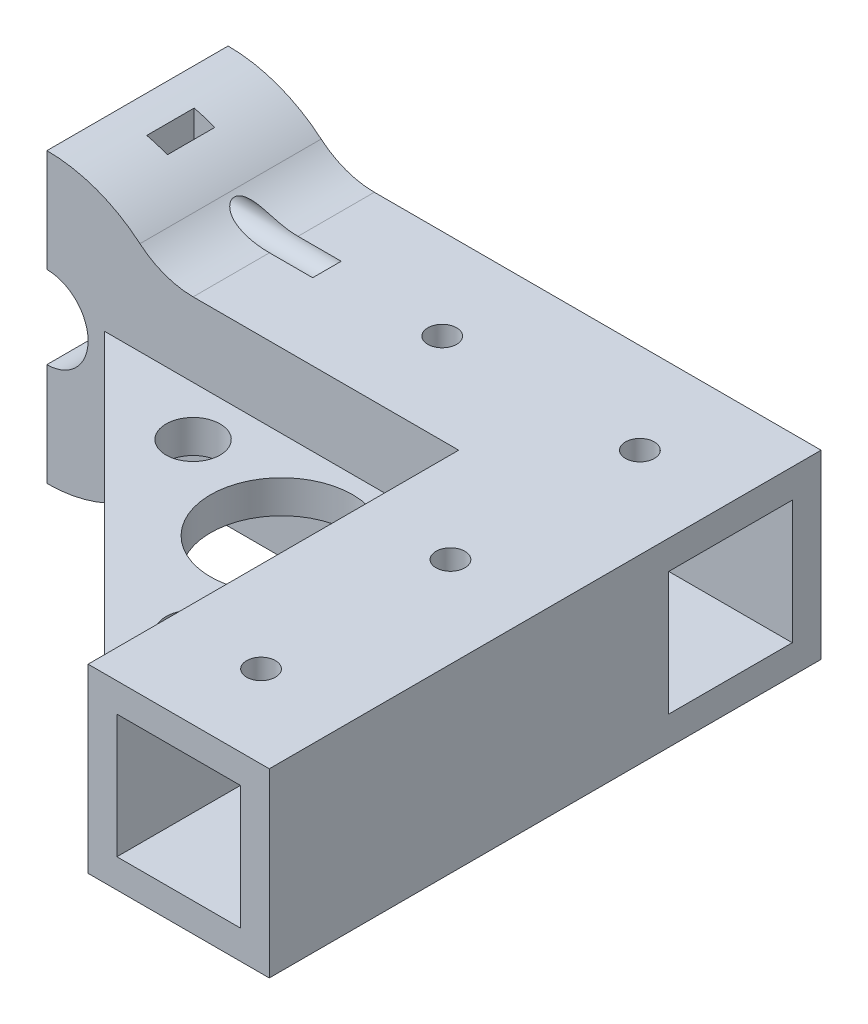
SolidWorks part; units mm, degrees
ref_plane "Front Plane" through (0, 0, 0) normal (0, 0, 1) x (1, 0, 0)
ref_plane "Top Plane" through (0, 0, 0) normal (0, 1, 0) x (1, 0, 0)
ref_plane "Right Plane" through (0, 0, 0) normal (1, 0, 0) x (0, 0, -1)
sketch "Sketch1" plane through (0, 0, 0) normal (0, 0, 1) x (1, 0, 0)
  line L0 (41.5599, 4.1233) -> (41.5599, -17.8767) construction
  line L1 (5.1706, 4.1233) -> (63.5599, 4.1233)
  line L2 (-8.4401, 7.6443) -> (-8.4401, -1.8767)
  line L3 (5.1706, -17.8767) -> (63.5599, -17.8767)
  line L4 (63.5599, 4.1233) -> (63.5599, -17.8767)
  line L5 (-8.4401, -11.8767) -> (-8.4401, -14.3557)
  line L6 (-8.4401, -14.3557) -> (-8.4401, -24.3767)
  line L7 (-8.4401, 7.6443) -> (-8.4401, 10.6233)
  arc A0 (-8.4401, -11.8767) -> (-8.4401, -1.8767) centre (-8.4401, -6.8767) ccw
  arc A1 (5.1706, 4.1233) -> (-8.4401, 10.6233) centre (-8.4401, -6.8767) ccw
  arc A2 (-8.4401, -24.3767) -> (5.1706, -17.8767) centre (-8.4401, -6.8767) ccw
  dimension "D4" = 10
  dimension "D5" = 35
  dimension "D1" = 22
  dimension "D2" = 50
  dimension "D3" = 22
  dimension "D6" = 11
extrude "Boss-Extrude1" add sketch "Sketch1" along normal blind 22
sketch "Sketch2" plane through (0, 0, 22) normal (0, 0, 1) x (1, 0, 0)
  line L0 (5.1706, -17.8767) -> (63.5599, -17.8767) construction
  line L1 (63.5599, 4.1233) -> (41.5599, 4.1233)
  line L2 (63.5599, 4.1233) -> (63.5599, -17.8767)
  line L3 (63.5599, -17.8767) -> (41.5599, -17.8767)
  line L4 (41.5599, 4.1233) -> (41.5599, -17.8767)
  dimension "D1" = 22
extrude "Boss-Extrude2" add sketch "Sketch2" along normal blind 45
sketch "Sketch3" plane through (0, 0, 67) normal (0, 0, 1) x (1, 0, 0)
  line L0 (63.5599, -17.8767) -> (63.5599, 4.1233) construction
  line L1 (45.0599, 0.6233) -> (60.0599, 0.6233)
  line L2 (45.0599, 0.6233) -> (45.0599, -14.3767)
  line L3 (45.0599, -14.3767) -> (60.0599, -14.3767)
  line L4 (60.0599, 0.6233) -> (60.0599, -14.3767)
  line L5 (63.5599, 4.1233) -> (41.5599, 4.1233) construction
  dimension "D1" = 15
  dimension "D2" = 3.5
  dimension "D3" = 15
  dimension "D4" = 3.5
extrude "Cut-Extrude1" cut sketch "Sketch3" against normal offset from surface (43 mm away) 2 up to face at (8.2716, -5.5017, 22)
sketch "Sketch4" plane through (63.5599, 0, 0) normal (1, 0, 0) x (0, 0, -1)
  line L0 (-67, 4.1233) -> (0, 4.1233) construction
  line L1 (-3.5, 0.6233) -> (-18.5, 0.6233)
  line L2 (-3.5, 0.6233) -> (-3.5, -14.3767)
  line L3 (-3.5, -14.3767) -> (-18.5, -14.3767)
  line L4 (-18.5, 0.6233) -> (-18.5, -14.3767)
  line L5 (0, -17.8767) -> (0, 4.1233) construction
  dimension "D1" = 15
  dimension "D2" = 15
  dimension "D3" = 3.5
  dimension "D4" = 3.5
extrude "Cut-Extrude2" cut sketch "Sketch4" against normal blind 45
ref_plane "Plane1" through (0, -6.8767, 0) normal (0, 1, 0) x (1, 0, 0)
sketch "Sketch6" plane through (0, -6.8767, 0) normal (0, 1, 0) x (1, 0, 0)
  line L0 (-1.4401, -22) -> (41.5599, -65)
  line L1 (41.5599, -22) -> (5.1706, -22) construction
  line L2 (41.5599, -67) -> (41.5599, -22) construction
  line L3 (41.5599, -65) -> (41.5599, -22)
  line L4 (41.5599, -22) -> (-1.4401, -22)
  line L5 (-3.4401, -22) -> (-3.4401, 0) construction
  dimension "D1" = 2
  dimension "D2" = 45
extrude "Boss-Extrude3" add sketch "Sketch6" along normal blind 2 and the other way blind 2
fillet "Fillet1" radius 10 2 edges at (5.1706, -17.8767, 11) (5.1706, 4.1233, 11)
sketch "Sketch5" plane through (-8.4401, 0, 0) normal (-1, 0, 0) x (0, 0, 1)
  line L0 (0, 4.3733) -> (22, 4.3733) construction
  line L1 (0, 10.6233) -> (0, -1.8767) construction
  line L2 (22, 10.6233) -> (22, -1.8767) construction
  line L3 (0, -18.1267) -> (22, -18.1267) construction
  line L4 (0, -11.8767) -> (0, -24.3767) construction
  line L5 (22, -11.8767) -> (22, -24.3767) construction
  circle A1 centre (11, 4.3733) radius 1.75
  circle A3 centre (11, -18.1267) radius 1.75
  dimension "D1" = 3.5
  dimension "D4" = 11
  dimension "D5" = 11
extrude "Cut-Extrude3" cut sketch "Sketch5" against normal blind 23
sketch "Sketch7" plane through (0, 4.1233, 0) normal (0, 1, 0) x (1, 0, 0)
  line L1 (14.5599, -9.2679) -> (14.5599, -12.7321) construction
  line L2 (-4.4401, -8.125) -> (-1.9401, -8.125)
  line L3 (-4.4401, -8.125) -> (-4.4401, -13.875)
  line L4 (-4.4401, -13.875) -> (-1.9401, -13.875)
  line L5 (-1.9401, -8.125) -> (-1.9401, -13.875)
  line L7 (-8.4401, -22) -> (-8.4401, 0) construction
  point P0 (14.5599, -11)
  dimension "D1" = 5.75
  dimension "D2" = 2.875
  dimension "D3" = 4
  dimension "D4" = 2.5
extrude "Cut-Extrude4" cut sketch "Sketch7" against normal blind 3.5 and the other way blind 10
mirror "Mirror1" about plane through (0, -6.8767, 0) normal (0, 1, 0) of "Cut-Extrude4"
sketch "Sketch8" plane through (0, -17.8767, 0) normal (0, -1, 0) x (1, 0, 0)
  line L0 (18.5599, 11) -> (63.5599, 11) construction
  line L1 (18.5599, 18.5) -> (18.5599, 3.5) construction
  line L2 (63.5599, 67) -> (63.5599, 0) construction
  line L3 (52.5599, 24) -> (52.5599, 67) construction
  line L4 (60.0599, 24) -> (45.0599, 24) construction
  line L5 (41.5599, 67) -> (63.5599, 67) construction
  circle A0 centre (28.5599, 11) radius 1.75
  circle A1 centre (52.5599, 11) radius 1.75
  circle A2 centre (52.5599, 34) radius 1.75
  circle A3 centre (52.5599, 57) radius 1.75
  dimension "D1" = 3.5
  dimension "D2" = 10
  dimension "D3" = 10
  dimension "D4" = 10
extrude "Cut-Extrude5" cut sketch "Sketch8" against normal up to surface (22 mm away) up to face at (29.2743, 4.1233, 24.45)
sketch "Sketch9" plane through (0, 0, 0) normal (0, 0, -1) x (-1, 0, 0)
  line L0 (-63.5599, -12.8767) -> (-9.3152, -12.8767) construction
  line L1 (-63.5599, -17.8767) -> (-63.5599, 4.1233) construction
  line L2 (-9.3152, -17.8767) -> (-63.5599, -17.8767) construction
  text T0 "  MR.3" font "Arial Narrow" height 12
  dimension "D1" = 5
extrude "Cut-Extrude6" cut sketch "Sketch9" against normal blind 1.5
sketch "Sketch10" plane through (0, -8.8767, 0) normal (0, -1, 0) x (1, 0, 0)
  line L0 (41.5599, 22) -> (20.0599, 43.5) construction
  line L1 (-1.4401, 22) -> (41.5599, 65) construction
  line L2 (41.5599, 67) -> (41.5599, 22) construction
  line L3 (41.5599, 22) -> (-1.4401, 22) construction
  circle A0 centre (30.8099, 32.75) radius 8.6369
  circle A1 centre (35.5599, 48.25) radius 3.2807
  circle A2 centre (15.3099, 28) radius 3.2807
  dimension "D1" = 6
  dimension "D2" = 6
  dimension "D3" = 15.5
  dimension "D4" = 15.5
extrude "Cut-Extrude7" cut sketch "Sketch10" against normal up to surface (4 mm away) up to face at (27.2266, -4.8767, 36.3333)
